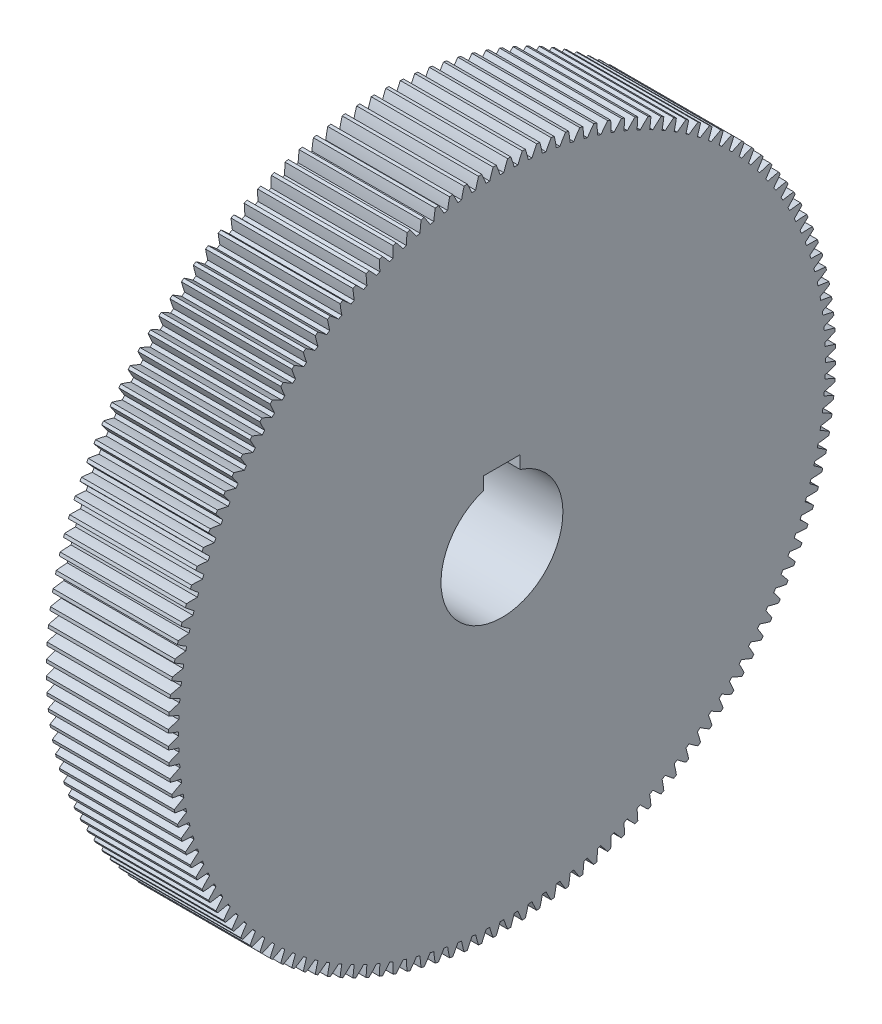
SolidWorks part; units mm, degrees
ref_plane "Plane1" through (0, 0, 0) normal (0, 0, 1) x (1, 0, 0)
ref_plane "Plane2" through (0, 0, 0) normal (0, 1, 0) x (1, 0, 0)
ref_plane "Plane3" through (0, 0, 0) normal (1, 0, 0) x (0, 0, -1)
sketch "HoldingSke" plane through (0, 0, 0) normal (0, 1, 0) x (1, 0, 0)
  line L0 (0, 0) -> (-0.5393, -0.3919)
  line L1 (-15, 0) -> (100, 0) construction
  line L2 (0, 0) -> (-2.1039, 2.3779)
  line L3 (0, 0) -> (-11.863, 4.5341)
  line L4 (0, 0) -> (-6.9867, 5.0761)
  line L5 (0, 0) -> (-46.8476, -17.4728)
  line L6 (0, 0) -> (-33.1585, -22.3721)
  line L7 (-2.1039, 2.3779) -> (8.6586, 51.2059)
  line L8 (-76.2, 54.61) -> (-72.9, 54.61)
  line L9 (-71.009, 38.7566) -> (-53.1078, 45.2721)
  line L10 (-76.2, 71.12) -> (104.1128, 71.12)
  line L11 (0, 0) -> (-40, 0)
  line L12 (-76.2, 101.6) -> (-76.147, 101.6)
  line L13 (24.9733, 27.94) -> (52.9518, 28.4284)
  line L14 (24.9733, 27.94) -> (24.9743, 27.94)
  line L15 (24.9733, 27.94) -> (100.4006, 29.5858)
  line L16 (-63.627, -1.5) -> (-12.827, -1.5)
  circle A0 centre (0, 0) radius 20
  circle A1 centre (0, 0) radius 37.5
  circle A2 centre (0, 0) radius 37.5
  circle A3 centre (0, 0) radius 20
  dimension "Num_teeth" = 144
  dimension "Pitch_radius" = 180.3128
  dimension "Width" = 40
  dimension "Thickness" = 40
sketch "BasProSke" plane through (0, 0, 0) normal (0, 1, 0) x (1, 0, 0)
  line L0 (-10, 0) -> (60, 0) construction
  line L1 (0, 0) -> (0, 109.5)
  line L2 (0, 0) -> (40, 0)
  line L3 (40, 0) -> (40, 109.5)
  line L4 (40, 109.5) -> (0, 109.5)
  dimension "Thickness" = 40
  dimension "Diameter" = 219
revolve "Base-Revolve" add sketch "BasProSke" angle 360 about L0
sketch "TooCutSke" plane through (0, 0, 0) normal (1, 0, 0) x (0, 0, -1)
  line L1 (0, 0) -> (0, 107) construction
  line L2 (0, 0) -> (-1.2708, 107.9925) construction
  line L3 (0, 0) -> (-4.7118, 215.9377) construction
  line L4 (-1.2708, 107.9925) -> (-2.3559, 107.9688) construction
  arc A0 (0.6043, 106.1223) -> (-0.6043, 106.1223) centre (0, 0) ccw
  arc A1 (1.8841, 109.5092) -> (-1.8841, 109.5092) centre (0, 0) ccw
  circle A2 centre (0, 0) radius 108 construction
  circle A3 centre (0, 0) radius 101.4868 construction
  arc A4 (-0.6043, 106.1223) -> (-1.8841, 109.5092) centre (-41.6202, 92.5599) ccw
  arc A5 (1.8841, 109.5092) -> (0.6043, 106.1223) centre (41.6202, 92.5599) ccw
extrude "ToothCut" cut sketch "TooCutSke" along normal through all
fillet "Breaks" [suppressed] radius 0.03 tangent propagation no
fillet "RootFillets" [suppressed] radius 0.376
pattern_circular "TeethCuts" count 144 every 2.5 about axis through (-10, 0, 0) along (1, 0, 0) of "ToothCut", "RootFillets", "Breaks"
sketch "HubNeaOneSke" plane through (0, 0, 0) normal (-1, 0, 0) x (0, 0, 1)
  circle A0 centre (0, 0) radius 37.5
  dimension "Diameter" = 75
extrude "HubNearOne" [suppressed] add sketch "HubNeaOneSke" along normal blind 10.0001
sketch "HubNeaBotSke" plane through (0, 0, 0) normal (-1, 0, 0) x (0, 0, 1)
  circle A0 centre (0, 0) radius 37.5
  dimension "Diameter" = 75
extrude "HubNearBoth" [suppressed] add sketch "HubNeaBotSke" along normal blind 5
ref_plane "FarPln" through (40, 0, 0) normal (1, 0, 0) x (0, 0, -1)
sketch "HubFarSke" plane through (40, 0, 0) normal (1, 0, 0) x (0, 0, -1)
  circle A0 centre (0, 0) radius 37.5
  dimension "Diameter" = 75
extrude "HubFar" [suppressed] add sketch "HubFarSke" along normal blind 5
sketch "BorSke" plane through (0, 0, 0) normal (1, 0, 0) x (0, 0, -1)
  circle A0 centre (0, 0) radius 20
  dimension "Diameter" = 40
extrude "Bore" cut sketch "BorSke" along normal mid plane 100.0001
sketch "KeySke" plane through (0, 0, 0) normal (1, 0, 0) x (0, 0, -1)
  line L0 (-6, 0) -> (-6, 23.3)
  line L1 (-6, 23.3) -> (6, 23.3)
  line L2 (6, 23.3) -> (6, 0)
  line L3 (0, 0) -> (0, 34) construction
  line L4 (-6, 0) -> (6, 0)
  dimension "Width" = 12
extrude "Keyway" cut sketch "KeySke" along normal mid plane 100.0001
pattern_circular "Keyway2" [suppressed] count 2 every 90 about axis through (-10, 0, 0) along (1, 0, 0) reverse direction yes
equation "' \"Module@HoldingSke\" = 6.35"
equation "' \"Num_teeth@HoldingSke\" = 12"
equation "' \"Ap@HoldingSke\" =  20"
equation "' \"Ap@HoldingSke\" = 20"
equation "' \"Width@HoldingSke\" = 0.5 * 25.4"
equation "' \"Hub_dia@HoldingSke\"= 1 * 25.4"
equation "' \"Hub_dia@HoldingSke\" = 1 * 25.4"
equation "' \"Overall_len@HoldingSke\" = 1.0 * 25.4"
equation "' \"Bore@HoldingSke\" = 0.75 * 25.4"
equation "' \"T_dim@HoldingSke\" = 0.1 * 25.4"
equation "' \"Width@KeySke\" = 0.25 * 25.4"
equation "' \"Show_teeth@HoldingSke\" = 13"
equation "' \"Backlash@HoldingSke\" = 0.009 * 25.4"
equation "' \"Addendum_fac@HoldingSke\" = 1.0"
equation "' \"Dedendum_fac@HoldingSke\" = 1.25"
equation "' \"Dedendum_add@HoldingSke\" = 0.00005 * 25.4"
equation "' \"Clearance_fac@HoldingSke\" = 0.25"
equation "\"Pitch@HoldingSke\" = 1 / \"Module@HoldingSke\""
equation "\"Overcut_dia@TooCutSke\" = (\"Num_teeth@HoldingSke\" + 2 * \"Addendum_fac@HoldingSke\") / \"Pitch@HoldingSke\" + 0.002 * 25.4"
equation "\"Pitch_dia@TooCutSke\" = \"Num_teeth@HoldingSke\" / \"Pitch@HoldingSke\""
equation "\"Base_dia@TooCutSke\" = \"Num_teeth@HoldingSke\" / \"Pitch@HoldingSke\" * cos((\"Ap@HoldingSke\"  * 3.14159265 / 180))"
equation "\"Root_dia@TooCutSke\" = (\"Num_teeth@HoldingSke\" + 2) / \"Pitch@HoldingSke\" - 2 * (\"Addendum_fac@HoldingSke\" + \"Dedendum_fac@HoldingSke\") / \"Pitch@HoldingSke\" - \"Dedendum_add@HoldingSke\" * 2"
equation "\"Half_ang@TooCutSke\" = 180 / \"Num_teeth@HoldingSke\""
equation "\"Half_CT@TooCutSke\" = \"Num_teeth@HoldingSke\" / \"Pitch@HoldingSke\" * sin((3.14159265 / 2 / \"Num_teeth@HoldingSke\")) / 2 - 7 * \"Backlash@HoldingSke\" / 4"
equation "\"Flank_rad@TooCutSke\" = \"Num_teeth@HoldingSke\" / \"Pitch@HoldingSke\" / 5"
equation "\"Radius@RootFillets\" = \"Clearance_fac@HoldingSke\" / \"Pitch@HoldingSke\" + \"Dedendum_add@HoldingSke\""
equation "\"Break_rad@Breaks\" = 0.02 / \"Pitch@HoldingSke\""
equation "\"Thickness@HoldingSke\" = \"Width@HoldingSke\""
equation "\"OAL@HoldingSke\" = \"Thickness@HoldingSke\""
equation "\"MHD@HoldingSke\" = (\"Num_teeth@HoldingSke\" + 2) / \"Pitch@HoldingSke\" - 2 * (\"Addendum_fac@HoldingSke\" + \"Dedendum_fac@HoldingSke\")  / \"Pitch@HoldingSke\" - \"Dedendum_add@HoldingSke\" * 2"
equation "\"MBD@HoldingSke\" = (\"Num_teeth@HoldingSke\" + 2) / \"Pitch@HoldingSke\" - 2 * (\"Addendum_fac@HoldingSke\" + \"Dedendum_fac@HoldingSke\")  / \"Pitch@HoldingSke\" - \"Dedendum_add@HoldingSke\" * 2 - 0.002 * 25.4"
equation "\"MHD@HoldingSke\" = ((sgn( \"MHD@HoldingSke\" - \"Hub_dia@HoldingSke\" )-1)*( \"MHD@HoldingSke\" - \"Hub_dia@HoldingSke\" ))/-2+ \"Hub_dia@HoldingSke\""
equation "\"MBD@HoldingSke\" = ((sgn( \"MBD@HoldingSke\" - \"Bore@HoldingSke\" )-1)*( \"MBD@HoldingSke\" - \"Bore@HoldingSke\" ))/-2+ \"Bore@HoldingSke\""
equation "\"OAL@HoldingSke\" = ((sgn( \"OAL@HoldingSke\" - \"Overall_len@HoldingSke\" )+1)*( \"OAL@HoldingSke\" - \"Overall_len@HoldingSke\" ))/2 + \"Overall_len@HoldingSke\" + 0.000002 * 25.4"
equation "\"Num_teeth@TeethCuts\" = int( \"Show_teeth@HoldingSke\" ) + 1"
equation "\"Num_teeth@TeethCuts\" = ((sgn( \"Num_teeth@TeethCuts\" - \"Num_teeth@HoldingSke\" )-1)*( \"Num_teeth@TeethCuts\" - \"Num_teeth@HoldingSke\" ))/-2+ \"Num_teeth@HoldingSke\""
equation "\"Num_teeth@TeethCuts\" = ((sgn( \"Num_teeth@TeethCuts\" - 2.0)+1)*( \"Num_teeth@TeethCuts\" - 2.0))/2 +2.0"
equation "\"Angle@TeethCuts\" = 360.0 / \"Num_teeth@HoldingSke\""
equation "\"Diameter@BasProSke\" = (\"Num_teeth@HoldingSke\" + 2 * \"Addendum_fac@HoldingSke\") / \"Pitch@HoldingSke\""
equation "\"Thickness@BasProSke\"  = \"Thickness@HoldingSke\""
equation "' \"Fillet_rad@BasProSke\" =  \"Thickness@HoldingSke\" * 0.05"
equation "' \"Fillet_rad@BasProSke\" = \"Thickness@HoldingSke\" * 0.05"
equation "\"MHD@HoldingSke\" = ((sgn( \"MHD@HoldingSke\" - \"Root_dia@TooCutSke\" )-1)*( \"MHD@HoldingSke\" - \"Root_dia@TooCutSke\" ))/-2+ \"Root_dia@TooCutSke\""
equation "\"Diameter@HubNeaOneSke\" = \"MHD@HoldingSke\""
equation "\"Length@HubNearOne\" = \"OAL@HoldingSke\" - \"Thickness@BasProSke\""
equation "\"Diameter@HubNeaBotSke\" = \"MHD@HoldingSke\""
equation "\"Length@HubNearBoth\" = ( \"OAL@HoldingSke\" - \"Thickness@BasProSke\" ) / 2.0"
equation "\"Thickness@FarPln\" = \"Thickness@BasProSke\""
equation "\"Diameter@HubFarSke\" = \"MHD@HoldingSke\""
equation "\"Length@HubFar\" = ( \"OAL@HoldingSke\" - \"Thickness@BasProSke\" ) / 2.0"
equation "\"Diameter@BorSke\" = \"MBD@HoldingSke\""
equation "\"D1@Bore\" = \"OAL@HoldingSke\" * 2.0"
equation "\"D1@Keyway\" = \"OAL@HoldingSke\" * 2.0"
equation "\"Offset@KeySke\" = \"T_dim@HoldingSke\" + \"MBD@HoldingSke\" / 2.0"
